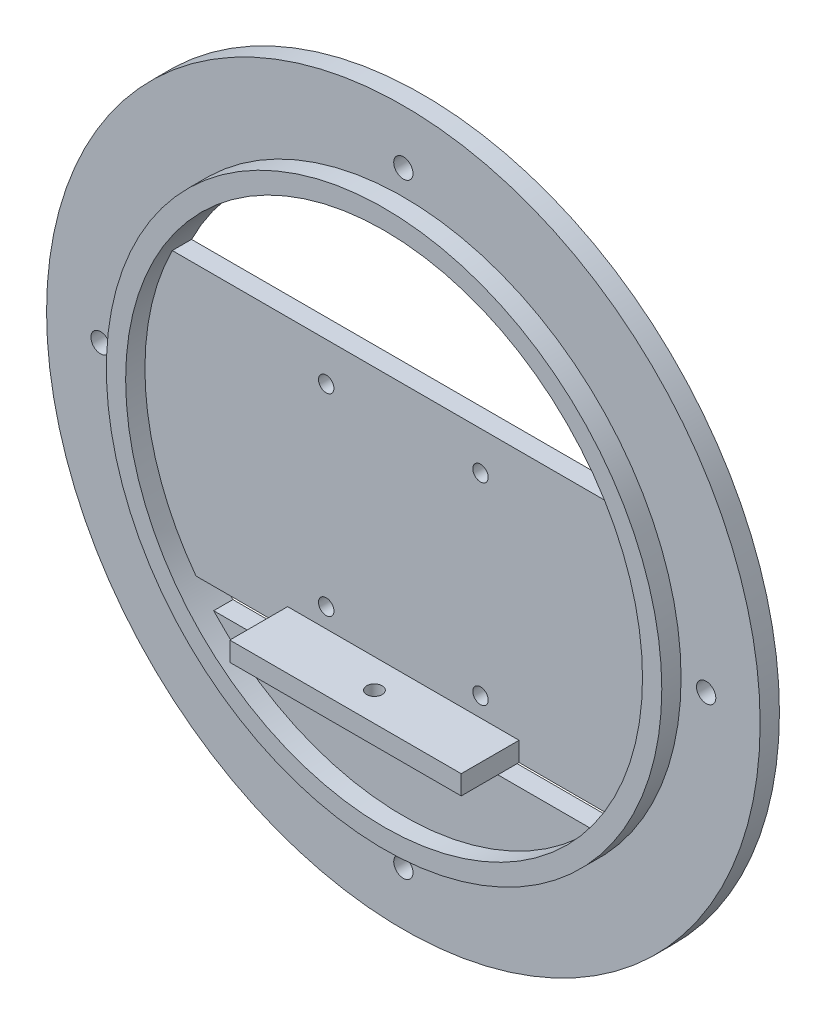
SolidWorks part; units mm, degrees
ref_plane "Front Plane" through (0, 0, 0) normal (0, 0, 1) x (1, 0, 0)
ref_plane "Top Plane" through (0, 0, 0) normal (0, 1, 0) x (1, 0, 0)
ref_plane "Right Plane" through (0, 0, 0) normal (1, 0, 0) x (0, 0, -1)
sketch "Sketch1" plane through (0, 0, 0) normal (0, 0, 1) x (1, 0, 0)
  circle A0 centre (0, 0) radius 92.5
  dimension "D1" = 185
extrude "Boss-Extrude1" add sketch "Sketch1" along normal blind 5
sketch "Sketch2" plane through (0, 0, 5) normal (0, 0, 1) x (1, 0, 0)
  circle A0 centre (0, 0) radius 72
  dimension "D1" = 144
extrude "Boss-Extrude2" add sketch "Sketch2" along normal blind 5
sketch "Sketch3" plane through (0, 0, 0) normal (0, 0, -1) x (-1, 0, 0)
  circle A0 centre (0, 0) radius 67
  dimension "D1" = 134
extrude "Cut-Extrude1" cut sketch "Sketch3" against normal through all
sketch "Sketch4" plane through (0, 0, 0) normal (0, 0, -1) x (-1, 0, 0)
  line L0 (92.5, 0) -> (-92.5, 0) construction
  line L5 (0, -92.5) -> (0, 92.5) construction
  line L11 (70, 30) -> (-70, 30)
  line L12 (70, 30) -> (70, -40)
  line L13 (70, -40) -> (-70, -40)
  line L14 (-70, 30) -> (-70, -40)
  circle A0 centre (0, 0) radius 92.5 construction
  dimension "D1" = 70
  dimension "D2" = 40
  dimension "D3" = 30
  dimension "D4" = 140
  dimension "D5" = 70
  dimension "D6" = 70
extrude "Boss-Extrude3" add sketch "Sketch4" against normal blind 5
sketch "Sketch6" plane through (0, 0, 5) normal (0, 0, 1) x (1, 0, 0)
  line L0 (0, -40) -> (0, 30) construction
  line L1 (53.7494, -40) -> (-53.7494, -40) construction
  line L2 (-59.9083, 30) -> (59.9083, 30) construction
  line L3 (-92.5, 0) -> (92.5, 0) construction
  line L5 (30, -40) -> (-30, -40)
  line L6 (30, -40) -> (30, -35)
  line L7 (30, -35) -> (-30, -35)
  line L8 (-30, -40) -> (-30, -35)
  circle A0 centre (0, 0) radius 92.5 construction
  dimension "D1" = 30
  dimension "D2" = 60
  dimension "D3" = 30
  dimension "D4" = 5
fillet "Fillet1" radius 2.5 1 edges at (0, -40, 0)
sketch "Sketch7" plane through (0, 0, 0) normal (0, 0, -1) x (-1, 0, 0)
  line L0 (0, 92.5) -> (0, -92.5) construction
  line L1 (92.5, 0) -> (-92.5, 0) construction
  line L2 (53.7494, -40) -> (-53.7494, -40) construction
  line L3 (-55, -45.5) -> (55, -45.5)
  line L4 (-55, -45.5) -> (-55, -70.5)
  line L5 (-55, -70.5) -> (55, -70.5)
  line L6 (55, -45.5) -> (55, -70.5)
  circle A0 centre (0, 0) radius 92.5 construction
  dimension "D1" = 110
  dimension "D2" = 8
  dimension "D3" = 25
  dimension "D4" = 55
  dimension "D5" = 5.5
extrude "Boss-Extrude5" add sketch "Sketch7" against normal blind 5
sketch "Sketch11" plane through (0, 0, 0) normal (0, 0, -1) x (-1, 0, 0)
  line L0 (-92.5, 0) -> (92.5, 0) construction
  line L1 (0, -92.5) -> (0, 90.9687) construction
  line L2 (70, 30) -> (-70, 30) construction
  circle A0 centre (0, 0) radius 92.5 construction
  circle A1 centre (-20, -30) radius 2
  circle A2 centre (-20, 20) radius 2
  circle A3 centre (20, 20) radius 2
  circle A4 centre (20, -30) radius 2
  dimension "D7" = 4
  dimension "D8" = 4
  dimension "D9" = 4
  dimension "D10" = 4
  dimension "D1" = 40
  dimension "D2" = 20
  dimension "D3" = 20
  dimension "D4" = 20
  dimension "D5" = 20
  dimension "D6" = 20
  dimension "D11" = 40
  dimension "D12" = 50
  dimension "D13" = 50
  dimension "D14" = 10
  dimension "D15" = 10
extrude "Cut-Extrude4" cut sketch "Sketch11" against normal up to surface (5 mm away) up to face at (0, -5.4361, 5)
sketch "Sketch12" plane through (0, 0, 0) normal (0, 0, -1) x (-1, 0, 0)
  line L0 (0, -92.5) -> (0, 92.5) construction
  line L1 (92.5, 0) -> (-92.5, 0) construction
  circle A0 centre (0, 0) radius 92.5 construction
  circle A1 centre (0, -78.5) radius 2.5
  circle A2 centre (-78.5, 0) radius 2.5
  circle A3 centre (0, 78.5) radius 2.5
  circle A4 centre (78.5, 0) radius 2.5
  dimension "D1" = 5
  dimension "D2" = 5
  dimension "D3" = 5
  dimension "D4" = 5
  dimension "D5" = 78.5
  dimension "D6" = 78.5
  dimension "D7" = 78.5
  dimension "D8" = 78.5
extrude "Cut-Extrude5" cut sketch "Sketch12" against normal up to surface (5 mm away) up to face at (72, 0, 5)
extrude "Boss-Extrude6" add sketch "Sketch6" along normal blind 15
sketch "Sketch13" plane through (0, -40, 0) normal (0, -1, 0) x (1, 0, 0)
  line L0 (0, 20) -> (0, 0) construction
  line L1 (-30, 20) -> (30, 20) construction
  line L2 (-70, 0) -> (70, 0) construction
  circle A0 centre (0, 12.5) radius 2
  dimension "D2" = 4
  dimension "D1" = 7.5
extrude "Cut-Extrude6" cut sketch "Sketch13" against normal up to surface (5 mm away) up to face at (0, -35, 12.5)
